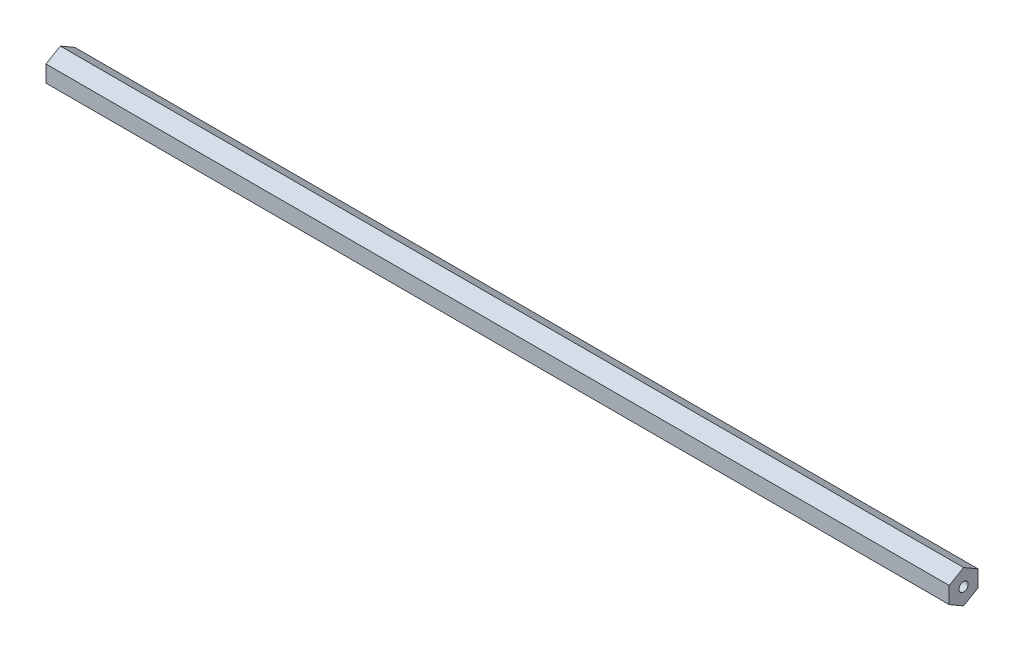
SolidWorks part; units mm, degrees
material "7075-T6 (SN)"
ref_plane "Front Plane" through (0, 0, 0) normal (0, 0, 1) x (1, 0, 0)
ref_plane "Top Plane" through (0, 0, 0) normal (0, 1, 0) x (1, 0, 0)
ref_plane "Right Plane" through (0, 0, 0) normal (1, 0, 0) x (0, 0, -1)
sketch "Sketch1" plane through (0, 0, 0) normal (1, 0, 0) x (0, 0, -1)
  line L1 (0, 7.3323) -> (-6.35, 3.6662)
  line L2 (-6.35, 3.6662) -> (-6.35, -3.6662)
  line L3 (-6.35, -3.6662) -> (0, -7.3323)
  line L4 (0, -7.3323) -> (6.35, -3.6662)
  line L5 (6.35, -3.6662) -> (6.35, 3.6662)
  line L6 (6.35, 3.6662) -> (0, 7.3323)
  circle A2 centre (0, 0) radius 6.35 construction
  dimension "D2" = 12.7
extrude "Boss-Extrude1" add sketch "Sketch1" along normal mid plane 398.526 contours L5 L6 L1 L2 L3 L4 region at (0, 0, 0)
hole_wizard "#10-32 Tapped Hole2" positions "3DSketch2" profile "Sketch5" tap size "#10-32" standard "ANSI Inch"
sketch3d "3DSketch2"
  point P0 (199.263, 0, 0)
  point P12 (-199.263, 0, 0)
sketch "Sketch5" plane through (199.263, 0, 0) normal (0, 1, 0) x (0, 0, -1)
  line L0 (0, 0) -> (0, 17.5608)
  line L1 (0, 17.5608) -> (2.0193, 16.3474)
  line L2 (2.0193, 16.3474) -> (2.0193, 0)
  line L5 (2.0193, 0) -> (0, 0)
  line L10 (0, 17.5608) -> (-2.0193, 16.3474) construction
  line L11 (0, -6.35) -> (0, 107.95) construction
  dimension "Tap Drill Dia." = 4.0386
  dimension "Tap Drill Depth" = 16.3474
  dimension "Drill Angle" = 118
cosmetic thread "Hole Thread3" parameters "D1"=13.97, "D2"=4.826
cosmetic thread "Hole Thread4" parameters "D1"=13.97, "D2"=4.826
